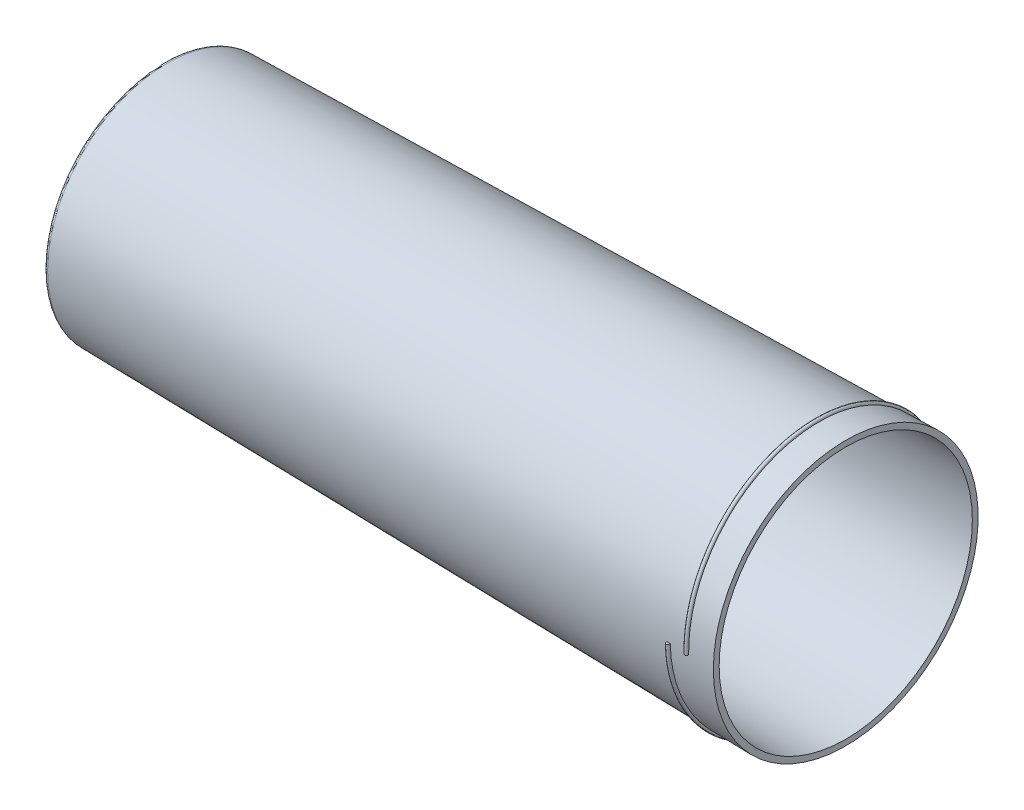
SolidWorks part; units mm, degrees
ref_plane "前视基准面" through (0, 0, 0) normal (0, 0, 1) x (1, 0, 0)
ref_plane "上视基准面" through (0, 0, 0) normal (0, 1, 0) x (1, 0, 0)
ref_plane "右视基准面" through (0, 0, 0) normal (1, 0, 0) x (0, 0, -1)
sketch "草图1" plane through (0, 0, 0) normal (0, 0, 1) x (1, 0, 0)
  line L0 (-14.4837, -3.3583) -> (2.0163, -3.3583) construction
  line L1 (-14.5006, -0.4583) -> (1.9994, -0.1583)
  line L2 (1.9994, -0.1583) -> (2.0163, -3.3583) construction
  line L3 (-14.5006, -0.4583) -> (-14.4837, -3.3583) construction
  line L4 (-14.3606, -0.5983) -> (1.9994, -0.2983)
  line L6 (1.9994, -0.1583) -> (1.9994, -0.2983)
  line L7 (-14.3575, -3.3583) -> (-14.2037, -3.3583)
  arc A0 (-14.5006, -0.4583) -> (-14.3575, -3.3583) centre (-33.9169, -2.8699) cw
  arc A1 (-14.3606, -0.5983) -> (-14.2037, -3.3583) centre (-28.8829, -2.8084) cw
revolve "旋转3" add sketch "草图1" angle 360 about L0
sketch "草图4" plane through (1.9994, 0, 0) normal (1, 0, 0) x (0, 0, -1)
  circle A0 centre (0, -3.3583) radius 3.2
ref_plane "基准面3" through (1.8, 0, 0) normal (1, 0, 0) x (0, 0, -1)
sketch "草图6" plane through (1.8, 0, 0) normal (1, 0, 0) x (0, 0, -1)
  circle A0 centre (0, -3.3583) radius 3.2
curve "螺旋线/涡状线2" pitch 0.45 height 0.45 radius 3.2 centre (1.8, -3.3583, 0) axis (-1, 0, 0) start towards (0, 0, -1)
ref_plane "基准面4" through (0, -3.35, 0) normal (0, 1, 0) x (1, 0, 0)
sketch "草图9" plane through (0, -3.35, 0) normal (0, 1, 0) x (1, 0, 0)
  circle A0 centre (1.3496, -3.1997) radius 0.0429
sweep "扫描1" add profiles "草图9" path "螺旋线/涡状线2"
fillet "圆角3" radius 0.1 1 edges at (-14.5006, -3.3583, 2.9)
ref_plane "基准面6" through (-0.0575, 0, -3.1626) normal (-0.0182, 0, -0.9998) x (-0.9998, 0, 0.0182)
